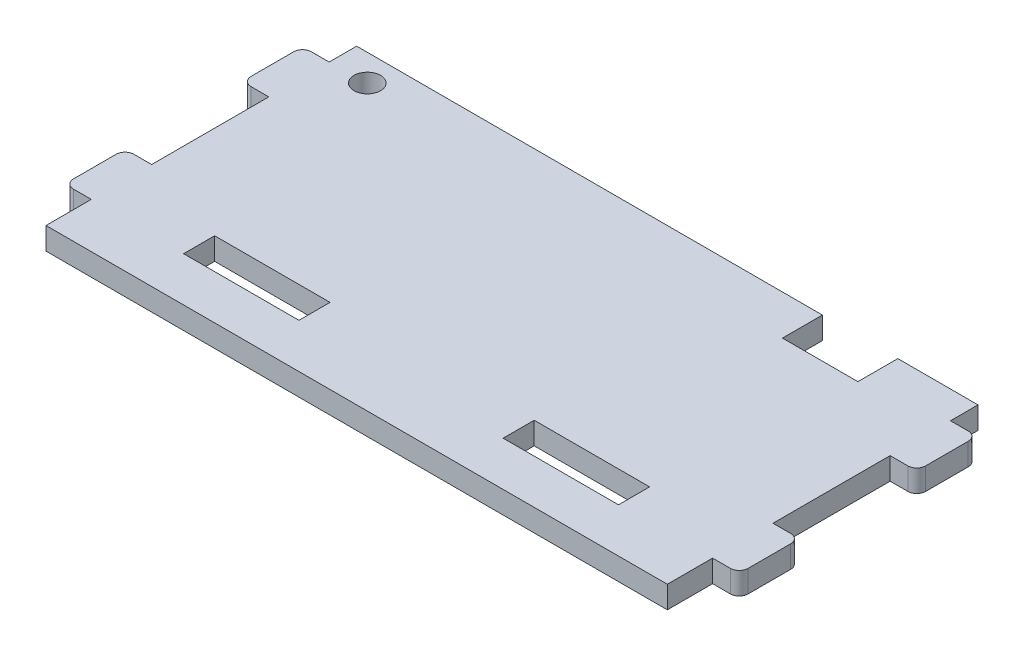
SolidWorks part; units mm, degrees
ref_plane "前视" through (0, 0, 0) normal (0, 0, 1) x (1, 0, 0)
ref_plane "上视" through (0, 0, 0) normal (0, 1, 0) x (1, 0, 0)
ref_plane "右视" through (0, 0, 0) normal (1, 0, 0) x (0, 0, -1)
sketch "草图1" plane through (0, 0, 0) normal (0, 1, 0) x (1, 0, 0)
  line L1 (-38, 17.5) -> (38, 17.5)
  line L2 (-38, 17.5) -> (-38, -17.5)
  line L3 (-38, -17.5) -> (38, -17.5)
  line L4 (38, 17.5) -> (38, -17.5)
  line L5 (-38, 17.5) -> (38, -17.5) construction
  line L6 (-38, -17.5) -> (38, 17.5) construction
  point P0 (0, 0)
  dimension "D1" = 35
  dimension "D2" = 76
extrude "凸台-拉伸1" add sketch "草图1" along normal blind 2.5
sketch "草图2" plane through (0, 2.5, 0) normal (0, 1, 0) x (1, 0, 0)
  line L0 (-38, -17.5) -> (38, -17.5) construction
  line L1 (-24.5, -9) -> (-11.5, -9)
  line L2 (-24.5, -9) -> (-24.5, -12.5)
  line L3 (-24.5, -12.5) -> (-11.5, -12.5)
  line L4 (-11.5, -9) -> (-11.5, -12.5)
  line L5 (-24.5, -9) -> (-11.5, -12.5) construction
  line L6 (-24.5, -12.5) -> (-11.5, -9) construction
  line L7 (-38, 17.5) -> (-38, -17.5) construction
  line L8 (0, 0) -> (0, -2.6782) construction
  line L9 (24.5, -12.5) -> (11.5, -12.5)
  line L10 (11.5, -9) -> (11.5, -12.5)
  line L11 (24.5, -9) -> (11.5, -9)
  line L12 (24.5, -9) -> (24.5, -12.5)
  point P0 (-18, -10.75)
  dimension "D1" = 5
  dimension "D2" = 13.5
  dimension "D3" = 13
  dimension "D4" = 3.5
extrude "切除-拉伸1" cut sketch "草图2" against normal through all
sketch "草图3" plane through (0, 2.5, 0) normal (0, 1, 0) x (1, 0, 0)
  line L0 (-38, -17.5) -> (-35, -17.5)
  line L1 (-38, -17.5) -> (38, -17.5) construction
  line L2 (-35, -17.5) -> (-35, -12.4)
  line L3 (-35, -12.4) -> (-38, -12.4)
  line L4 (-38, 17.5) -> (-38, -17.5) construction
  line L5 (-38, -12.4) -> (-38, -17.5)
  line L6 (-38, 17.5) -> (-35, 17.5)
  line L7 (38, 17.5) -> (-38, 17.5) construction
  line L8 (-35, 17.5) -> (-35, 14.4)
  line L9 (-35, 14.4) -> (-38, 14.4)
  line L10 (-38, 14.4) -> (-38, 17.5)
  line L11 (-38, 7.6) -> (-35, 7.6)
  line L12 (-35, 7.6) -> (-35, -5.6)
  line L13 (-35, -5.6) -> (-38, -5.6)
  line L14 (-38, -5.6) -> (-38, 7.6)
  line L15 (0, 0) -> (0, 5.419) construction
  line L16 (38, -17.5) -> (35, -17.5)
  line L17 (38, -12.4) -> (38, -17.5)
  line L18 (35, -17.5) -> (35, -12.4)
  line L19 (35, -12.4) -> (38, -12.4)
  line L20 (35, -5.6) -> (38, -5.6)
  line L21 (38, -5.6) -> (38, 7.6)
  line L22 (35, 7.6) -> (35, -5.6)
  line L23 (38, 7.6) -> (35, 7.6)
  line L24 (35, 14.4) -> (38, 14.4)
  line L25 (35, 17.5) -> (35, 14.4)
  line L26 (38, 17.5) -> (35, 17.5)
  line L27 (38, 14.4) -> (38, 17.5)
  dimension "D1" = 3
  dimension "D2" = 5.1
  dimension "D3" = 3
  dimension "D4" = 3.1
  dimension "D5" = 3
  dimension "D6" = 6.8
  dimension "D7" = 6.8
extrude "切除-拉伸2" cut sketch "草图3" against normal through all
fillet "圆角1" radius 1 8 edges at (38, 1.25, -14.4) (38, 1.25, -7.6) (38, 1.25, 5.6) (38, 1.25, 12.4) (-38, 1.25, 12.4) (-38, 1.25, 5.6) (-38, 1.25, -7.6) (-38, 1.25, -14.4)
sketch "草图4" plane through (0, 2.5, 0) normal (0, 1, 0) x (1, 0, 0)
  line L0 (35, 17.5) -> (-35, 17.5) construction
  line L1 (35, 17.5) -> (35, 14.4) construction
  line L2 (-35, 14.4) -> (-35, 17.5) construction
  line L3 (18.0812, 14.5) -> (26.9965, 14.5) construction
  line L4 (25.9681, 17.5) -> (25.9681, 13)
  line L5 (25.9681, 13) -> (17.4681, 13)
  line L6 (17.4681, 13) -> (17.4681, 17.5)
  line L7 (17.4681, 17.5) -> (25.9681, 17.5)
  circle A0 centre (-30.8, 14.5) radius 1.5
  point P4 (-35, 15.95)
  point P11 (35, 15.95)
  dimension "D1" = 3
  dimension "D2" = 4.2
  dimension "D3" = 4.5
  dimension "D4" = 8.5
  dimension "D5" = 9.0319
extrude "切除-拉伸3" cut sketch "草图4" against normal through all
